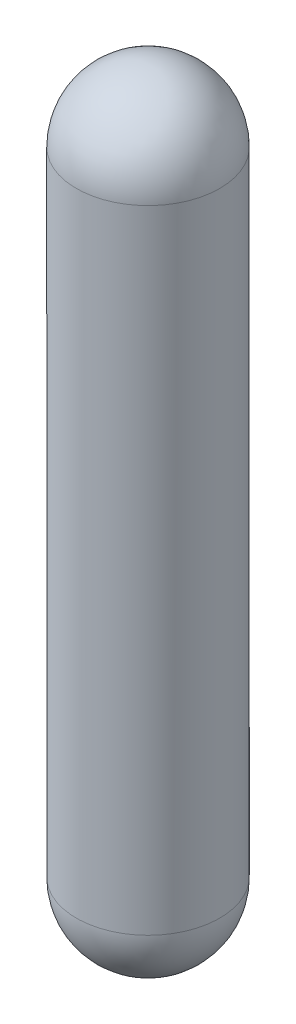
SolidWorks part; units mm, degrees
other "Markup1"
sketch "Sketch2" plane through (-160, -160, 160) normal (0, 0, 1) x (1, 0, 0)
ref_plane "Front Plane" through (0, 0, 0) normal (0, 0, 1) x (1, 0, 0)
ref_plane "Top Plane" through (0, 0, 0) normal (0, 1, 0) x (1, 0, 0)
ref_plane "Right Plane" through (0, 0, 0) normal (1, 0, 0) x (0, 0, -1)
sketch "Sketch1" plane through (0, 0, 0) normal (0, 0, 1) x (1, 0, 0)
  line L0 (0, 1477.5) -> (0, 1645)
  line L2 (0, 0) -> (0, 1477.5)
  line L4 (167.5, 0) -> (167.5, 1477.5)
  line L5 (0, 0) -> (0, -167.5)
  line L6 (0, 738.4774) -> (167.5, 738.4774) construction
  arc A0 (0, -167.5) -> (167.5, 0) centre (0, 0) ccw
  arc A1 (167.5, 1477.5) -> (0, 1645) centre (0, 1477.5) ccw
  dimension "D1" = 167.5
  dimension "D2" = 1812.5
revolve "Revolve1" add sketch "Sketch1" angle 360 about L2
